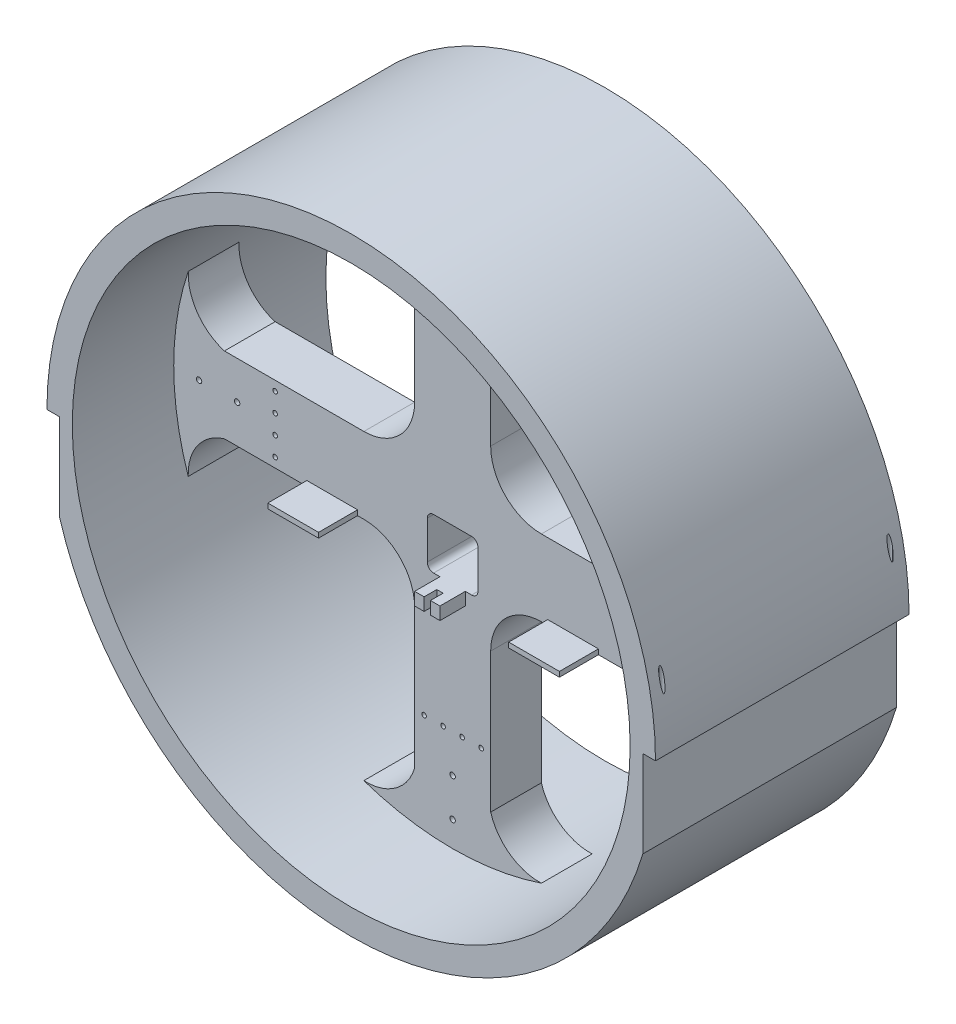
SolidWorks part; units mm, degrees
material "6061 Alloy"
ref_plane "Front Plane" through (0, 0, 0) normal (0, 0, 1) x (1, 0, 0)
ref_plane "Top Plane" through (0, 0, 0) normal (0, 1, 0) x (1, 0, 0)
ref_plane "Right Plane" through (0, 0, 0) normal (1, 0, 0) x (0, 0, -1)
sketch "Sketch1" plane through (0, 0, 0) normal (0, 0, 1) x (1, 0, 0)
  circle A0 centre (0, 0) radius 152.4
  circle A1 centre (0, 0) radius 139.7
  dimension "D1" = 304.8
  dimension "D2" = 279.4
extrude "Boss-Extrude1" add sketch "Sketch1" along normal mid plane 127
sketch "Sketch2" plane through (0, 0, 0) normal (0, 0, 1) x (1, 0, 0)
  line L0 (-114.3, 19.05) -> (-138.7192, 19.05)
  line L1 (-147.1918, -19.05) -> (147.1918, -19.05)
  line L2 (-147.1918, -19.05) -> (-147.1918, 19.05)
  line L3 (-147.1918, 19.05) -> (147.1918, 19.05)
  line L4 (147.1918, -19.05) -> (147.1918, 19.05)
  line L5 (-147.1918, -19.05) -> (147.1918, 19.05) construction
  line L6 (-147.1918, 19.05) -> (147.1918, -19.05) construction
  line L7 (19.05, -143.9568) -> (-19.05, -143.9568)
  line L8 (19.05, -143.9568) -> (19.05, 143.9568)
  line L9 (19.05, 143.9568) -> (-19.05, 143.9568)
  line L10 (-19.05, -143.9568) -> (-19.05, 143.9568)
  line L11 (19.05, -143.9568) -> (-19.05, 143.9568) construction
  line L12 (19.05, 143.9568) -> (-19.05, -143.9568) construction
  line L15 (-44.45, 19.05) -> (-19.05, 19.05)
  line L16 (-19.05, 44.45) -> (-19.05, 19.05)
  line L17 (-132.4254, 44.4927) -> (-143.3503, 19.05)
  line L18 (-143.3503, 19.05) -> (-138.7192, 19.05)
  line L19 (-138.7192, 19.05) -> (-143.3503, 19.05)
  line L20 (-19.05, 114.3) -> (-19.05, 143.9568)
  line L21 (-44.45, 132.4398) -> (-19.05, 143.9568)
  line L22 (44.45, 19.05) -> (19.05, 19.05)
  line L23 (19.05, 44.45) -> (19.05, 19.05)
  line L24 (19.05, 143.3503) -> (19.05, 138.7192)
  line L25 (19.05, 114.3) -> (19.05, 138.7192)
  line L26 (44.4927, 132.4254) -> (19.05, 143.3503)
  line L27 (114.3, 19.05) -> (143.9568, 19.05)
  line L28 (132.4398, 44.45) -> (143.9568, 19.05)
  line L29 (19.05, -44.45) -> (19.05, -19.05)
  line L30 (44.45, -19.05) -> (19.05, -19.05)
  line L31 (143.3503, -19.05) -> (138.7192, -19.05)
  line L32 (114.3, -19.05) -> (138.7192, -19.05)
  line L33 (132.4254, -44.4927) -> (143.3503, -19.05)
  line L34 (19.05, -114.3) -> (19.05, -143.9568)
  line L35 (44.45, -132.4398) -> (19.05, -143.9568)
  line L36 (-44.45, -19.05) -> (-19.05, -19.05)
  line L37 (-19.05, -44.45) -> (-19.05, -19.05)
  line L38 (-19.05, -143.3503) -> (-19.05, -138.7192)
  line L39 (-19.05, -114.3) -> (-19.05, -138.7192)
  line L40 (-44.4927, -132.4254) -> (-19.05, -143.3503)
  line L41 (-114.3, -19.05) -> (-143.9568, -19.05)
  line L42 (-132.4398, -44.45) -> (-143.9568, -19.05)
  arc A1 (-44.45, 19.05) -> (-19.05, 44.45) centre (-44.45, 44.45) ccw
  arc A2 (-114.3, 19.05) -> (-132.4254, 44.4927) centre (-107.0492, 43.3931) cw
  circle A3 centre (0, 0) radius 139.7 construction
  arc A5 (-19.05, 114.3) -> (-44.45, 132.4398) centre (-43.3968, 107.0616) ccw
  arc A6 (19.05, 44.45) -> (44.45, 19.05) centre (44.45, 44.45) ccw
  arc A7 (19.05, 114.3) -> (44.4927, 132.4254) centre (43.3931, 107.0492) cw
  arc A8 (114.3, 19.05) -> (132.4398, 44.45) centre (107.0616, 43.3968) ccw
  arc A9 (44.45, -19.05) -> (19.05, -44.45) centre (44.45, -44.45) ccw
  arc A10 (114.3, -19.05) -> (132.4254, -44.4927) centre (107.0492, -43.3931) cw
  arc A11 (19.05, -114.3) -> (44.45, -132.4398) centre (43.3968, -107.0616) ccw
  arc A12 (-19.05, -44.45) -> (-44.45, -19.05) centre (-44.45, -44.45) ccw
  arc A13 (-19.05, -114.3) -> (-44.4927, -132.4254) centre (-43.3931, -107.0492) cw
  arc A14 (-114.3, -19.05) -> (-132.4398, -44.45) centre (-107.0616, -43.3968) ccw
  point P0 (0, 0)
  point P6 (0, 0)
  point P67 (0, 0)
  dimension "D3" = 25.4
  dimension "D5" = 25.4
  dimension "D1" = 38.1
  dimension "D2" = 38.1
  dimension "D4" = 114.3
  dimension "D6" = 114.3
  dimension "D7" = 4
extrude "Boss-Extrude2" add sketch "Sketch2" along normal mid plane 25.4 contours L1 L10 L3 L2 | L10 L1 L8 L3 | L10 L3 L8 L9 | L8 L1 L4 L3 | L10 L7 L8 L1 | A14 L1 L42 | L10 A13 L40 | A11 L8 L35 | A9 L1 L8 | L1 A10 L33 | A8 L3 L28 | L8 A7 L26 | A5 L10 L21 | L0 A2 L17 L3 | A1 L3 L10 | A6 L8 L3 | A12 L10 L1 region at (-83.1209, 0, 0) region at (-132.2215, 26.1932, 0) region at (-24.7235, 24.7235, 0) region at (0, 81.5034, 0) region at (0, 0, 0) region at (24.7235, 24.7235, 0) region at (83.1209, 0, 0) region at (-24.7235, -24.7235, 0) region at (0, -81.5034, 0) region at (-26.2233, 132.4495, 0) region at (24.7235, -24.7235, 0) region at (-132.4495, -26.2233, 0) region at (132.4495, 26.2233, 0) region at (26.1932, 132.2215, 0) region at (-26.1932, -132.2215, 0) region at (132.2215, -26.1932, 0) region at (26.2233, -132.4495, 0)
sketch "Sketch4" plane through (0, 0, 0) normal (0, 0, 1) x (1, 0, 0)
  line L0 (-12.7, -24.892) -> (-12.7, 0.508)
  line L5 (-12.7, -24.892) -> (12.7, -24.892)
  line L6 (-12.7, 0.508) -> (12.7, 0.508)
  line L7 (12.7, -24.892) -> (12.7, 0.508)
  line L8 (-12.7, -24.892) -> (12.7, 0.508) construction
  line L9 (-12.7, 0.508) -> (12.7, -24.892) construction
  point P1 (0, -12.192)
  dimension "D1" = 25.4
  dimension "D2" = 25.4
  dimension "D3" = 0
  dimension "D4" = 0.508
extrude "Cut-Extrude3" cut sketch "Sketch4" against normal through all both and the other way through all
sketch "Sketch8" plane through (0, 0, 63.5) normal (0, 0, 1) x (1, 0, 0)
  line L0 (-146.05, 0) -> (-163.2527, 0)
  line L1 (-146.05, 0) -> (-146.05, -50.8)
  line L2 (-163.2527, 0) -> (-163.2527, -50.8)
  line L3 (-146.05, -50.8) -> (-163.2527, -50.8)
  circle A0 centre (0, 0) radius 152.4 construction
  dimension "D1" = 50.8
  dimension "D2" = 146.05
extrude "Cut-Extrude5" cut sketch "Sketch8" against normal through all
hole_wizard "#4-40 Tapped Hole2" positions "Sketch21" profile "Sketch22" tap size "#4-40" standard "ANSI Inch" end condition through all
sketch "Sketch21" plane through (0, 0, 0) normal (0, -1, 0) x (-1, 0, 0)
  line L0 (146.05, -63.5) -> (152.4, -63.5) construction
  line L1 (146.05, 63.5) -> (152.4, 63.5) construction
  line L2 (152.4, 63.5) -> (152.4, -63.5) construction
  point P0 (149.225, 57.15)
  point P2 (149.225, -57.15)
  dimension "D1" = 6.35
  dimension "D2" = 6.35
  dimension "D3" = 3.175
  dimension "D4" = 3.175
sketch "Sketch22" plane through (-149.225, 0, -57.15) normal (1, 0, 0) x (0, 0, -1)
  line L0 (0, 0) -> (0, 152.4)
  line L1 (0, 152.4) -> (1.1303, 152.4)
  line L2 (1.1303, 152.4) -> (1.1303, 0)
  line L5 (1.1303, 0) -> (0, 0)
  line L11 (0, -6.35) -> (0, 107.95) construction
  dimension "Thru Tap Drill Dia." = 2.2606
  dimension "Thru Tap Drill Depth" = 152.4
cosmetic thread "Hole Thread7" parameters "D2"=2.8448
cosmetic thread "Hole Thread8" parameters "D2"=2.8448
mirror "Mirror1" about plane through (0, 0, 0) normal (1, 0, 0) of "#4-40 Tapped Hole2", "Cut-Extrude5"
hole_wizard "#4-40 Tapped Hole1" positions "Sketch11" profile "Sketch12" tap size "#4-40" standard "ANSI Inch" end condition through all
sketch "Sketch11" plane through (0, 0, 12.7) normal (0, 0, 1) x (1, 0, 0)
  line L1 (44.45, 19.05) -> (114.3, 19.05) construction
  point P4 (88.9, 14.2875)
  point P6 (88.9, 4.7625)
  point P17 (88.9, -4.7625)
  point P19 (88.9, -14.2875)
  dimension "D1" = 88.9
  dimension "D2" = 88.9
  dimension "D3" = 88.9
  dimension "D4" = 9.525
  dimension "D5" = 88.9
  dimension "D6" = 9.525
  dimension "D7" = 4.7625
  dimension "D8" = 9.525
sketch "Sketch12" plane through (88.9, 14.2875, 12.7) normal (1, 0, 0) x (0, -1, 0)
  line L0 (0, 0) -> (0, 76.2)
  line L1 (0, 76.2) -> (1.1303, 76.2)
  line L2 (1.1303, 76.2) -> (1.1303, 0)
  line L5 (1.1303, 0) -> (0, 0)
  line L11 (0, -6.35) -> (0, 107.95) construction
  dimension "Thru Tap Drill Dia." = 2.2606
  dimension "Thru Tap Drill Depth" = 76.2
cosmetic thread "Hole Thread1" parameters "D2"=2.8448
cosmetic thread "Hole Thread2" parameters "D2"=2.8448
cosmetic thread "Hole Thread3" parameters "D2"=2.8448
cosmetic thread "Hole Thread4" parameters "D2"=2.8448
hole_wizard "#6-32 Tapped Hole1" positions "Sketch13" profile "Sketch14" tap size "#6-32" standard "ANSI Inch" end condition through all
sketch "Sketch13" plane through (0, 0, 12.7) normal (0, 0, 1) x (1, 0, 0)
  point P0 (-107.95, 0)
  point P2 (-127, 0)
  dimension "D1" = 107.95
  dimension "D2" = 19.05
sketch "Sketch14" plane through (-107.95, 0, 12.7) normal (1, 0, 0) x (0, -1, 0)
  line L0 (0, 0) -> (0, 76.2)
  line L1 (0, 76.2) -> (1.3525, 76.2)
  line L2 (1.3525, 76.2) -> (1.3525, 0)
  line L5 (1.3525, 0) -> (0, 0)
  line L11 (0, -6.35) -> (0, 107.95) construction
  dimension "Thru Tap Drill Dia." = 2.7051
  dimension "Thru Tap Drill Depth" = 76.2
cosmetic thread "Hole Thread5" parameters "D2"=3.5052
cosmetic thread "Hole Thread6" parameters "D2"=3.5052
pattern_circular "CirPattern1" count 4 every 90 about axis through (0, 0, 63.5) along (0, 0, 1) of "#6-32 Tapped Hole1"
sketch "Sketch17" plane through (0, 0, 12.7) normal (0, 0, 1) x (1, 0, 0)
  line L0 (-12.7, -24.892) -> (12.7, -24.892) construction
  line L1 (-12.7, 0.508) -> (-12.7, -24.892) construction
  line L2 (-12.7, -21.717) -> (-12.7, -24.892)
  line L3 (-12.7, -24.892) -> (-9.525, -24.892)
  line L4 (12.7, 0.508) -> (-12.7, 0.508) construction
  line L5 (12.7, -24.892) -> (12.7, 0.508) construction
  line L6 (-12.7, -2.667) -> (-12.7, 0.508)
  line L7 (-12.7, 0.508) -> (-9.525, 0.508)
  line L8 (9.525, 0.508) -> (12.7, 0.508)
  line L9 (12.7, 0.508) -> (12.7, -2.667)
  line L10 (12.7, -21.717) -> (12.7, -24.892)
  line L11 (12.7, -24.892) -> (9.525, -24.892)
  arc A0 (-9.525, -24.892) -> (-12.7, -21.717) centre (-9.525, -21.717) cw
  arc A1 (-12.7, -2.667) -> (-9.525, 0.508) centre (-9.525, -2.667) cw
  arc A2 (9.525, 0.508) -> (12.7, -2.667) centre (9.525, -2.667) cw
  arc A3 (9.525, -24.892) -> (12.7, -21.717) centre (9.525, -21.717) ccw
  dimension "D1" = 3.175
  dimension "D4" = 3.175
  dimension "D5" = 3.175
  dimension "D6" = 3.175
  dimension "D12" = 3.175
  dimension "D2" = 3.175
  dimension "D3" = 3.175
  dimension "D7" = 3.175
  dimension "D8" = 3.175
  dimension "D9" = 3.175
  dimension "D10" = 3.175
  dimension "D11" = 3.175
  dimension "D13" = 0
extrude "Boss-Extrude4" add sketch "Sketch17" against normal up to surface (25.4 mm away) up to face at (1.3525, 107.95, -12.7)
sketch "Sketch18" plane through (0, 0, 12.7) normal (0, 0, 1) x (1, 0, 0)
  line L0 (-9.525, -24.892) -> (9.525, -24.892) construction
  line L1 (-6.35, -24.892) -> (6.35, -24.892)
  line L2 (-6.35, -24.892) -> (-6.35, -31.242)
  line L3 (-6.35, -31.242) -> (6.35, -31.242)
  line L4 (6.35, -24.892) -> (6.35, -31.242)
  line L5 (-12.7, -2.667) -> (-12.7, -21.717) construction
  dimension "D1" = 12.7
  dimension "D2" = 6.35
  dimension "D3" = 6.35
extrude "Boss-Extrude5" add sketch "Sketch18" along normal blind 12.7 and the other way blind 38.1
sketch "Sketch19" plane through (0, -24.892, 0) normal (0, 1, 0) x (1, 0, 0)
  line L0 (6.35, -25.4) -> (-6.35, -25.4) construction
  line L1 (-1.5875, -25.4) -> (1.5875, -25.4)
  line L2 (-1.5875, -25.4) -> (-1.5875, -19.05)
  line L3 (-1.5875, -19.05) -> (1.5875, -19.05)
  line L4 (1.5875, -25.4) -> (1.5875, -19.05)
  line L5 (-6.35, -12.7) -> (-6.35, -25.4) construction
  dimension "D1" = 3.175
  dimension "D2" = 4.7625
  dimension "D3" = 6.35
extrude "Cut-Extrude6" cut sketch "Sketch19" against normal up to next
sketch "Sketch20" plane through (0, -24.892, 0) normal (0, 1, 0) x (1, 0, 0)
  line L0 (6.35, 25.4) -> (-6.35, 25.4) construction
  line L1 (1.5875, 25.4) -> (-1.5875, 25.4)
  line L2 (1.5875, 25.4) -> (1.5875, 19.05)
  line L3 (1.5875, 19.05) -> (-1.5875, 19.05)
  line L4 (-1.5875, 25.4) -> (-1.5875, 19.05)
  line L5 (6.35, 25.4) -> (6.35, 12.7) construction
  dimension "D1" = 3.175
  dimension "D2" = 6.35
  dimension "D3" = 4.7625
extrude "Cut-Extrude7" cut sketch "Sketch20" against normal up to next
pattern_circular "CirPattern2" count 4 every 90 about axis through (0, 0, 63.5) along (0, 0, 1) of "#4-40 Tapped Hole1"
sketch "Sketch24" plane through (0, -19.05, 0) normal (0, -1, 0) x (1, 0, 0)
  line L1 (-73.025, -31.2594) -> (-47.625, -31.2594)
  line L2 (-73.025, -31.2594) -> (-73.025, 32.2406)
  line L3 (-73.025, 32.2406) -> (-47.625, 32.2406)
  line L4 (-47.625, -31.2594) -> (-47.625, 32.2406)
  line L5 (-73.025, -31.2594) -> (-47.625, 32.2406) construction
  line L6 (-73.025, 32.2406) -> (-47.625, -31.2594) construction
  point P0 (-60.325, 0.4906)
  dimension "D1" = 63.5
  dimension "D2" = 25.4
  dimension "D3" = 60.325
extrude "Boss-Extrude6" add sketch "Sketch24" against normal blind 2.54
mirror "Mirror2" about plane through (0, 0, 0) normal (1, 0, 0) of "Boss-Extrude6"
